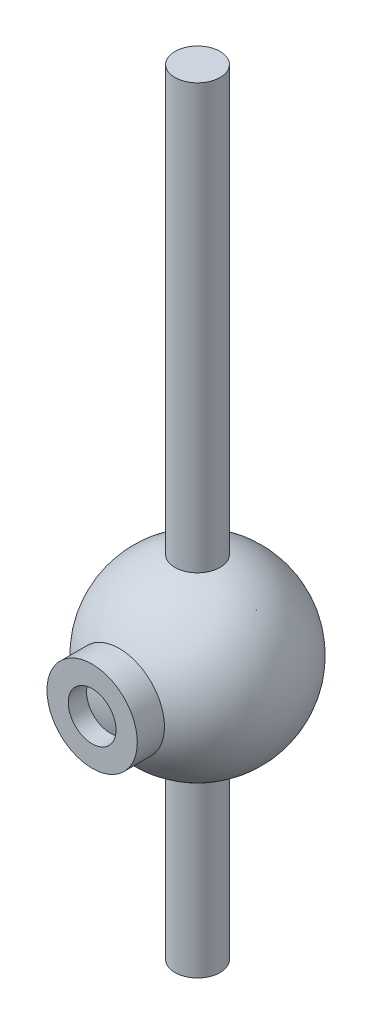
SolidWorks part; units mm, degrees
material "Plain Carbon Steel"
ref_plane "Front Plane" through (0, 0, 0) normal (0, 0, 1) x (1, 0, 0)
ref_plane "Top Plane" through (0, 0, 0) normal (0, 1, 0) x (1, 0, 0)
ref_plane "Right Plane" through (0, 0, 0) normal (1, 0, 0) x (0, 0, -1)
sketch "Sketch1" plane through (0, 0, 0) normal (0, 0, 1) x (1, 0, 0)
  circle A0 centre (0, 0) radius 6
  circle A1 centre (0, 0) radius 3.175
  dimension "D1" = 12
  dimension "D2" = 6.35
extrude "Boss-Extrude1" add sketch "Sketch1" along normal blind 7 from offset 7
sketch "Sketch2" plane through (0, 0, 0) normal (0, 0, 1) x (1, 0, 0)
  line L0 (0, -35) -> (0, 68) construction
  line L1 (0, -35) -> (3, -35)
  line L2 (3, -35) -> (3, -11.619)
  line L3 (3, 11.619) -> (3, 68)
  line L4 (3, 68) -> (0, 68)
  line L5 (0, 68) -> (0, -35)
  arc A0 (3, -11.619) -> (3, 11.619) centre (0, 0) ccw
revolve "Revolve1" add sketch "Sketch2" angle 360 about L0
